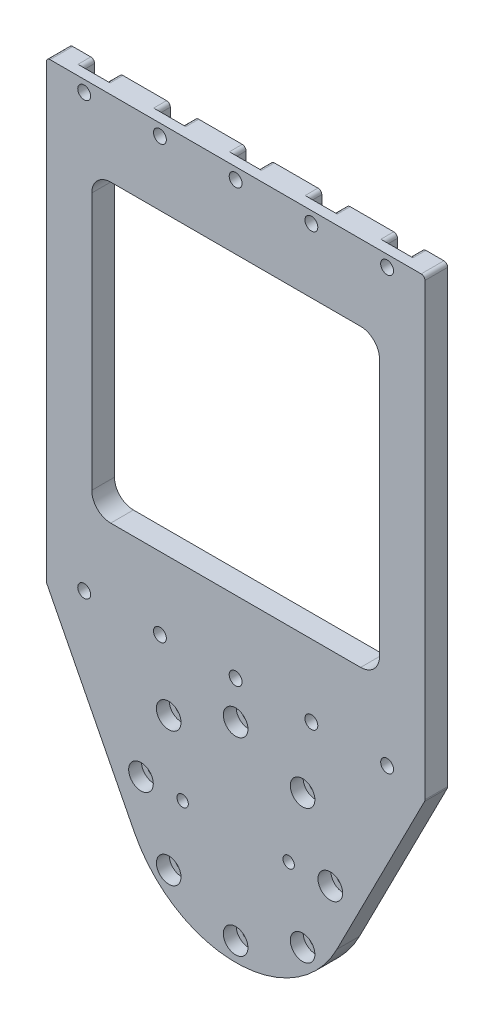
SolidWorks part; units mm, degrees
material "6061-T6 (SS)"
ref_plane "Front Plane" through (0, 0, 0) normal (0, 0, 1) x (1, 0, 0)
ref_plane "Top Plane" through (0, 0, 0) normal (0, 1, 0) x (1, 0, 0)
ref_plane "Right Plane" through (0, 0, 0) normal (1, 0, 0) x (0, 0, -1)
sketch "Sketch1" plane through (0, 0, 0) normal (0, 0, 1) x (1, 0, 0)
  line L0 (-30, 0) -> (-30, 152)
  line L1 (-30, 152) -> (30, 152)
  line L2 (30, 152) -> (30, 0)
  arc A0 (-30, 0) -> (30, 0) centre (0, 0) ccw
  dimension "D1" = 60
  dimension "D2" = 152
extrude "Boss-Extrude1" add sketch "Sketch1" along normal blind 6
sketch "Sketch7" plane through (0, 0, 6) normal (0, 0, 1) x (1, 0, 0)
  line L0 (-50, 32) -> (-26.7242, -13.6315)
  line L1 (30, 152) -> (50, 152)
  line L2 (30, 152) -> (30, 32)
  line L3 (30, 32) -> (50, 32) construction
  line L4 (50, 152) -> (50, 32)
  line L5 (-30, 152) -> (-50, 152)
  line L6 (-30, 152) -> (-30, 32)
  line L7 (-30, 32) -> (-50, 32) construction
  line L8 (-50, 152) -> (-50, 32)
  line L10 (26.7242, -13.6315) -> (50, 32)
  line L13 (30, 0) -> (30, 152)
  line L14 (30, 152) -> (-30, 152)
  line L15 (-30, 152) -> (-30, 0)
  line L16 (30, 0) -> (30, 152)
  line L17 (30, 152) -> (-30, 152)
  line L18 (-30, 152) -> (-30, 0)
  arc A1 (-30, 0) -> (30, 0) centre (0, 0) ccw
  arc A2 (-30, 0) -> (30, 0) centre (0, 0) ccw
  arc M9 (-30, 0) -> (30, 0) centre (0, 0) ccw
  line M10 (30, 0) -> (30, 152)
  line M12 (-30, 152) -> (-30, 0)
  dimension "D1" = 100
  dimension "D2" = 32
  dimension "D3" = 0
  dimension "D4" = 20
extrude "Boss-Extrude2" add sketch "Sketch7" against normal up to surface (6 mm away) contours L5 L8 L0 M9 M12 | L10 L4 L1 M9 M10 region at (-39.5172, 81.611, 6) region at (39.5172, 81.611, 6) up to face at (0, 68.5, 0)
sketch "Sketch2" plane through (0, 0, 6) normal (0, 0, 1) x (1, 0, 0)
  circle A0 centre (0, 0) radius 25
  point P6 (0, 25)
  point P12 (17.6777, 17.6777)
  point P13 (25, 0)
  point P14 (17.6777, -17.6777)
  point P15 (0, -25)
  point P16 (-17.6777, -17.6777)
  point P17 (-25, 0)
  point P18 (-17.6777, 17.6777)
  dimension "D1" = 50
  dimension "D2" = 8
hole_wizard "CBORE for M3 Hex Socket Head Cap Screw1" positions "Sketch2" profile "Sketch3" counterbore size "M3" standard "DIN" end condition through all
sketch "Sketch3" plane through (-17.6777, 17.6777, 6) normal (1, 0, 0) x (0, -1, 0)
  line L0 (0, 0) -> (0, 6)
  line L1 (0, 6) -> (1.7, 6)
  line L3 (1.7, 6) -> (1.7, 3.4)
  line L4 (1.7, 3.4) -> (3.25, 3.4)
  line L5 (3.25, 3.4) -> (3.25, 0)
  line L7 (3.25, 0) -> (0, 0)
  line L11 (0, -6.35) -> (0, 107.95) construction
  dimension "Thru Hole Dia." = 3.4
  dimension "Thru Hole Depth" = 6
  dimension "C'Bore Dia." = 6.5
  dimension "C'Bore Depth" = 3.4
sketch "Sketch4" plane through (0, 0, 0) normal (0, 0, -1) x (-1, 0, 0)
  line L0 (-50, 35) -> (50, 35) construction
  line L3 (-50, 152) -> (50, 152) construction
  line L4 (0, 152) -> (0, 149) construction
  line L8 (50, 32) -> (50, 152) construction
  line L9 (-50, 32) -> (-50, 152) construction
  point P7 (0, 35)
  point P23 (20, 35)
  point P24 (40, 35)
  point P25 (0, 35)
  point P26 (20, 35)
  point P27 (-20, 35)
  point P28 (0, 35)
  point P29 (-20, 35)
  point P30 (-40, 35)
  point P46 (0, 149)
  point P59 (20, 149)
  point P60 (40, 149)
  point P61 (0, 149)
  point P62 (20, 149)
  point P63 (-20, 149)
  point P64 (0, 149)
  point P65 (-20, 149)
  point P66 (-40, 149)
  dimension "D1" = 35
  dimension "D5" = 3
  dimension "D4" = 3
  dimension "D6" = 3
  dimension "D3" = 3
  dimension "D2" = 3
hole_wizard "CBORE for M3 Hex Socket Head Cap Screw2" positions "Sketch4" profile "Sketch6" counterbore size "M3" standard "DIN"
sketch "Sketch6" plane through (40, 149, 0) normal (1, 0, 0) x (0, 1, 0)
  line L0 (0, 0) -> (0, 11.0215)
  line L1 (0, 11.0215) -> (1.7, 10)
  line L2 (1.7, 10) -> (1.7, 3.4)
  line L3 (1.7, 3.4) -> (3.25, 3.4)
  line L4 (3.25, 3.4) -> (3.25, 0)
  line L5 (3.25, 0) -> (0, 0)
  line L10 (0, 11.0215) -> (-1.7, 10) construction
  line L11 (0, -6.35) -> (0, 107.95) construction
  dimension "Hole Dia." = 3.4
  dimension "Hole Depth" = 10
  dimension "C'Bore Dia." = 6.5
  dimension "C'Bore Depth" = 3.4
  dimension "Drill Angle" = 118
sketch "Sketch8" plane through (0, 0, 0) normal (0, 0, -1) x (-1, 0, 0)
  line L0 (50, 32) -> (50, 152) construction
  line L1 (-38, 132) -> (38, 132)
  line L2 (-38, 132) -> (-38, 54)
  line L3 (-38, 54) -> (38, 54)
  line L4 (38, 132) -> (38, 54)
  line L5 (-50, 152) -> (-50, 32) construction
  line L6 (-38.75, 152) -> (-21.25, 152) construction
  dimension "D1" = 12
  dimension "D2" = 12
  dimension "D3" = 20
  dimension "D4" = 78
extrude "Cut-Extrude1" cut sketch "Sketch8" against normal up to next and the other way through all
fillet "Fillet2" radius 5 4 edges at (-38, 54, 3) (38, 54, 3) (38, 132, 3) (-38, 132, 3)
sketch "Sketch11" plane through (0, 0, 0) normal (0, 0, -1) x (-1, 0, 0)
  circle A0 centre (0, 0) radius 14
  point P6 (-14, 0)
  point P8 (14, 0)
  dimension "D1" = 28
hole_wizard "Ø3.0mm Dowel Hole1" positions "Sketch11" profile "Sketch10" hole size "Ø3.0" standard "BSI" end condition through all
sketch "Sketch10" plane through (-14, 0, 0) normal (1, 0, 0) x (0, 1, 0)
  line L0 (0, 0) -> (0, 6)
  line L1 (0, 6) -> (1.5, 6)
  line L2 (1.5, 6) -> (1.5, 0)
  line L5 (1.5, 0) -> (0, 0)
  line L11 (0, -6.35) -> (0, 107.95) construction
  dimension "Thru Hole Dia." = 3
  dimension "Thru Hole Depth" = 6
sketch "Sketch12" plane through (0, 0, 0) normal (0, 0, -1) x (-1, 0, 0)
  line L0 (-43.25, 149) -> (-43.25, 152)
  line L1 (-43.25, 152) -> (-36.75, 152)
  line L2 (-36.75, 152) -> (-36.75, 149)
  line L3 (-38.75, 152) -> (-21.25, 152) construction
  line L4 (-23.25, 149) -> (-23.25, 152)
  line L5 (-23.25, 152) -> (-16.75, 152)
  line L6 (-16.75, 152) -> (-16.75, 149)
  line L7 (-3.25, 149) -> (-3.25, 152)
  line L8 (-3.25, 152) -> (3.25, 152)
  line L9 (3.25, 152) -> (3.25, 149)
  line L10 (16.75, 149) -> (16.75, 152)
  line L11 (16.75, 152) -> (23.25, 152)
  line L12 (23.25, 152) -> (23.25, 149)
  line L13 (36.75, 149) -> (36.75, 152)
  line L14 (36.75, 152) -> (43.25, 152)
  line L15 (43.25, 152) -> (43.25, 149)
  arc A0 (-41.25, 152) -> (-38.75, 152) centre (-40, 149) ccw construction
  arc A1 (-41.25, 152) -> (-38.75, 152) centre (-40, 149) ccw construction
  arc A2 (-43.25, 149) -> (-36.75, 149) centre (-40, 149) ccw
  arc A5 (-23.25, 149) -> (-16.75, 149) centre (-20, 149) ccw
  arc A6 (-3.25, 149) -> (3.25, 149) centre (0, 149) ccw
  arc A7 (16.75, 149) -> (23.25, 149) centre (20, 149) ccw
  arc A8 (36.75, 149) -> (43.25, 149) centre (40, 149) ccw
  dimension "D1" = 5
extrude "Cut-Extrude2" cut sketch "Sketch12" against normal up to surface (3.4 mm away) and the other way through all up to face at (38.3, 149, 3.4)
fillet "Fillet3" radius 1 14 edges at (23.25, 152, 1.7) (16.75, 152, 1.7) (3.25, 152, 1.7) (-3.25, 152, 1.7) (-16.75, 152, 1.7) (-23.25, 152, 1.7) (-36.75, 152, 1.7) (-43.25, 152, 1.7) (-50, 152, 3) (-50, 32, 3) (50, 32, 3) (50, 152, 3) (36.75, 152, 1.7) (43.25, 152, 1.7)
